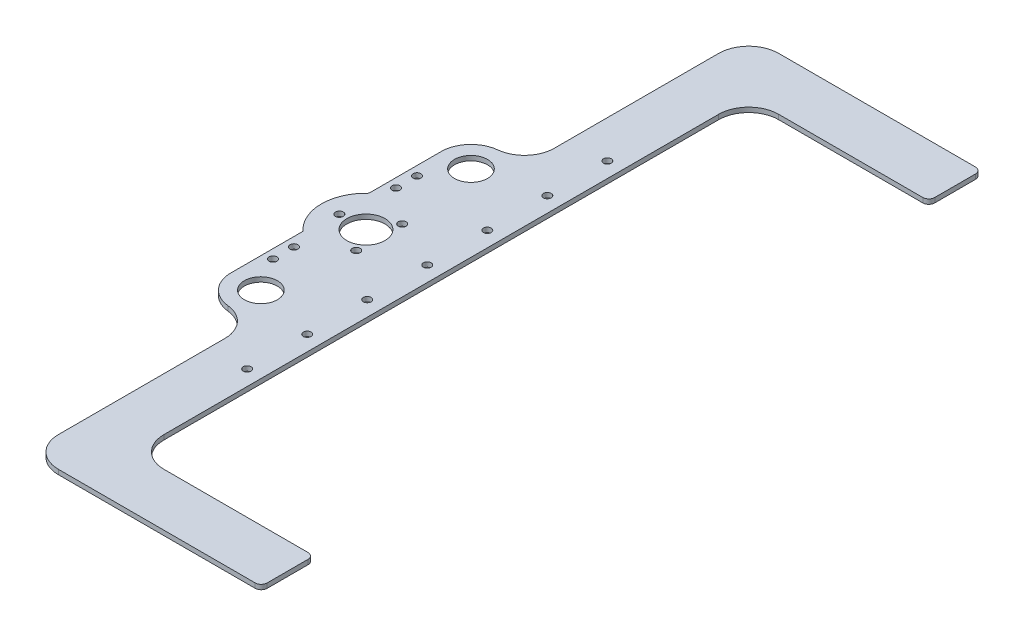
SolidWorks part; units mm, degrees
ref_plane "Front Plane" through (0, 0, 0) normal (0, 0, 1) x (1, 0, 0)
ref_plane "Top Plane" through (0, 0, 0) normal (0, 1, 0) x (1, 0, 0)
ref_plane "Right Plane" through (0, 0, 0) normal (1, 0, 0) x (0, 0, -1)
sketch "Sketch1" plane through (0, 0, 0) normal (0, 1, 0) x (1, 0, 0)
  line L0 (-67.9713, -52.7283) -> (-67.9713, -82.5864)
  line L1 (-45.2284, -108.5097) -> (-45.2284, -114.9973)
  line L3 (-22.9035, -128.2046) -> (-22.9035, 49.5954)
  line L5 (-45.2284, 37.4027) -> (-45.2284, 30.9152)
  line L6 (-67.9713, 4.9919) -> (-67.9713, -24.8662)
  line L7 (-45.2284, 49.5954) -> (-45.2284, 37.4027)
  line L13 (-22.9035, 49.5954) -> (-22.9035, 78.0705)
  line L14 (-22.9035, 113.0954) -> (-32.5284, 113.0954)
  line L15 (-45.2284, 49.5954) -> (-45.2284, 100.3954)
  line L16 (-45.2284, -114.9973) -> (-45.2284, -128.2046)
  line L19 (-45.2284, -128.2046) -> (-45.2284, -179.0046)
  line L20 (-32.5284, -191.7046) -> (-22.9035, -191.7046)
  line L21 (-22.9035, -128.2046) -> (-22.9035, -156.6798)
  line L22 (-22.9035, 113.0954) -> (53.2965, 113.0954)
  line L24 (-10.2035, 90.7705) -> (53.2965, 90.7705)
  line L25 (53.2965, 113.0954) -> (53.2965, 90.7705)
  line L26 (-22.9035, -191.7046) -> (53.2965, -191.7046)
  line L28 (-10.2035, -169.3798) -> (53.2965, -169.3798)
  line L29 (53.2965, -191.7046) -> (53.2965, -169.3798)
  arc A0 (-67.9713, -82.5864) -> (-56.6084, -95.8785) centre (-55.2885, -83.2473) ccw
  arc A1 (-45.2284, -108.5097) -> (-56.6084, -95.8785) centre (-57.9284, -108.5097) ccw
  arc A4 (-56.6084, 18.284) -> (-45.2284, 30.9152) centre (-57.9284, 30.9152) ccw
  arc A5 (-56.6084, 18.284) -> (-67.9713, 4.9919) centre (-55.2885, 5.6527) ccw
  arc A6 (-67.9713, -24.8662) -> (-67.9713, -52.7283) centre (-55.2885, -38.7973) ccw
  arc A22 (-45.2284, 100.3954) -> (-32.5284, 113.0954) centre (-32.5284, 100.3954) cw
  arc A23 (-45.2284, -179.0046) -> (-32.5284, -191.7046) centre (-32.5284, -179.0046) ccw
  arc A24 (-22.9035, 78.0705) -> (-10.2035, 90.7705) centre (-10.2035, 78.0705) cw
  arc A25 (-22.9035, -156.6798) -> (-10.2035, -169.3798) centre (-10.2035, -156.6798) ccw
  circle A30 centre (-55.2885, -83.2473) radius 6.985 construction
  circle A31 centre (-64.1613, -69.2773) radius 1.65 construction
  circle A32 centre (-64.1613, -60.3873) radius 1.65 construction
  circle A33 centre (-55.2885, -38.7973) radius 8.0645 construction
  circle A34 centre (-49.6688, -29.0636) radius 1.65 construction
  circle A35 centre (-49.6688, -48.531) radius 1.65 construction
  circle A36 centre (-66.528, -38.7973) radius 1.65 construction
  circle A37 centre (-64.1613, -17.2073) radius 1.65 construction
  circle A38 centre (-64.1613, -8.3173) radius 1.65 construction
  circle A39 centre (-55.2885, 5.6527) radius 6.985 construction
  circle A40 centre (-55.2885, -83.2473) radius 6.985
  circle A41 centre (-64.1613, -69.2773) radius 1.65
  circle A42 centre (-64.1613, -60.3873) radius 1.65
  circle A43 centre (-55.2885, -38.7973) radius 8.0645
  circle A44 centre (-49.6688, -29.0636) radius 1.65
  circle A45 centre (-49.6688, -48.531) radius 1.65
  circle A46 centre (-66.528, -38.7973) radius 1.65
  circle A47 centre (-64.1613, -17.2073) radius 1.65
  circle A48 centre (-64.1613, -8.3173) radius 1.65
  circle A49 centre (-55.2885, 5.6527) radius 6.985
  circle A50 centre (-29.342, 37.4027) radius 1.65 construction
  circle A51 centre (-29.342, 12.0027) radius 1.65 construction
  circle A52 centre (-29.342, -13.3973) radius 1.65 construction
  circle A53 centre (-29.342, -38.7973) radius 1.65 construction
  circle A54 centre (-29.342, -64.1973) radius 1.65 construction
  circle A55 centre (-29.342, -89.5973) radius 1.65 construction
  circle A56 centre (-29.342, -114.9973) radius 1.65 construction
  circle A57 centre (-29.342, 37.4027) radius 1.65
  circle A58 centre (-29.342, 12.0027) radius 1.65
  circle A59 centre (-29.342, -13.3973) radius 1.65
  circle A60 centre (-29.342, -38.7973) radius 1.65
  circle A61 centre (-29.342, -64.1973) radius 1.65
  circle A62 centre (-29.342, -89.5973) radius 1.65
  circle A63 centre (-29.342, -114.9973) radius 1.65
  point P58 (-45.2284, 113.0954)
  dimension "D37" = 63.5
  dimension "D44" = 12.7
  dimension "D45" = 12.7
  dimension "D46" = 12.7
  dimension "D47" = 12.7
  dimension "D1" = 177.8
  dimension "D2" = 32.385
  dimension "D30" = 304.8
  dimension "D31" = 22.3249
  dimension "D36" = 22.3249
  dimension "D38" = 22.3249
  dimension "D39" = 22.3249
  dimension "D40" = 76.2
  dimension "D41" = 76.2
extrude "Boss-Extrude1" add sketch "Sketch1" along normal blind 2
fillet "Fillet1" radius 2.54 4 edges at (53.2965, 1, -113.0954) (53.2965, 1, -90.7705) (53.2965, 1, 169.3798) (53.2965, 1, 191.7046)
